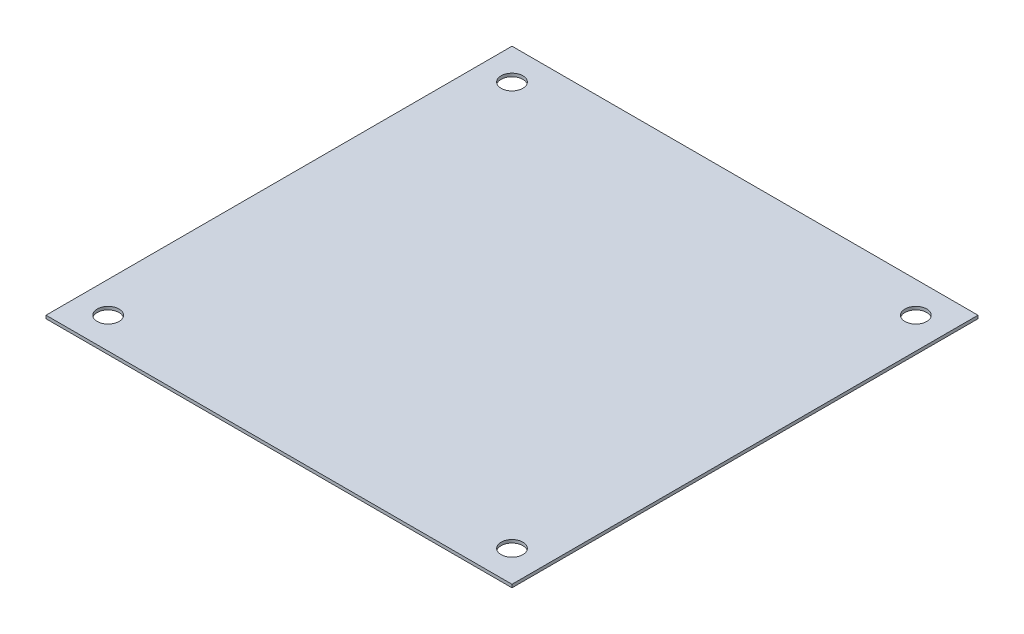
SolidWorks part; units mm, degrees
material "6061 Alloy"
ref_plane "Plano frontal" through (0, 0, 0) normal (0, 0, 1) x (1, 0, 0)
ref_plane "Plano superior" through (0, 0, 0) normal (0, 1, 0) x (1, 0, 0)
ref_plane "Plano direito" through (0, 0, 0) normal (1, 0, 0) x (0, 0, -1)
sketch "Sketch1" plane through (0, 0, 0) normal (0, 1, 0) x (1, 0, 0)
  line L1 (-75, -75) -> (75, -75)
  line L2 (-75, -75) -> (-75, 75)
  line L3 (-75, 75) -> (75, 75)
  line L4 (75, -75) -> (75, 75)
  line L5 (-75, -75) -> (75, 75) construction
  line L6 (-75, 75) -> (75, -75) construction
  point P0 (0, 0)
  dimension "D1" = 150
base flange "Base-Flange1" sketch "Sketch1" thickness 1 reverse thickness direction yes parameters "D1"=0.7366
sketch "Sketch6" plane through (0, 1, 0) normal (0, 1, 0) x (1, 0, 0)
  line L0 (75, 75) -> (-75, 75) construction
  line L1 (-75, 75) -> (-75, -75) construction
  line L2 (75, -75) -> (75, 75) construction
  line L3 (-75, -75) -> (75, -75) construction
  circle A0 centre (-65, -65) radius 3.5
  circle A1 centre (-65, 65) radius 3.5
  circle A2 centre (65, 65) radius 3.5
  circle A3 centre (65, -65) radius 3.5
  dimension "D1" = 10
  dimension "D5" = 7
  dimension "D2" = 10
  dimension "D3" = 10
  dimension "D4" = 10
extrude "Cut-Extrude1" cut sketch "Sketch6" against normal up to surface (1 mm away) normal cut yes up to face at (0, 0, 0)
sketch "Bend-Lines1" plane through (0, 0, 0) normal (0, 1, 0) x (1, 0, 0)
sketch "Bounding-Box1" plane through (0, 0, 0) normal (0, 1, 0) x (1, 0, 0)
sheet metal parameters "Sheet-Metal(1)" thickness 1 parameters "D1"=0.7366
flat pattern "Flat-Pattern(1)" [suppressed]
sketch "Bend-Lines2" plane through (0, 0, 0) normal (0, 1, 0) x (1, 0, 0)
sketch "Bounding-Box2" [suppressed] plane through (0, 0, 0) normal (0, 1, 0) x (1, 0, 0)
sheet metal parameters "Sheet-Metal(2)" thickness 1 parameters "D1"=0.7366
flat pattern "Flat-Pattern(1)"
sketch "Bend-Lines2" plane through (0, 0, 0) normal (0, 1, 0) x (1, 0, 0)
sketch "Bounding-Box2" [suppressed] plane through (0, 0, 0) normal (0, 1, 0) x (1, 0, 0)
